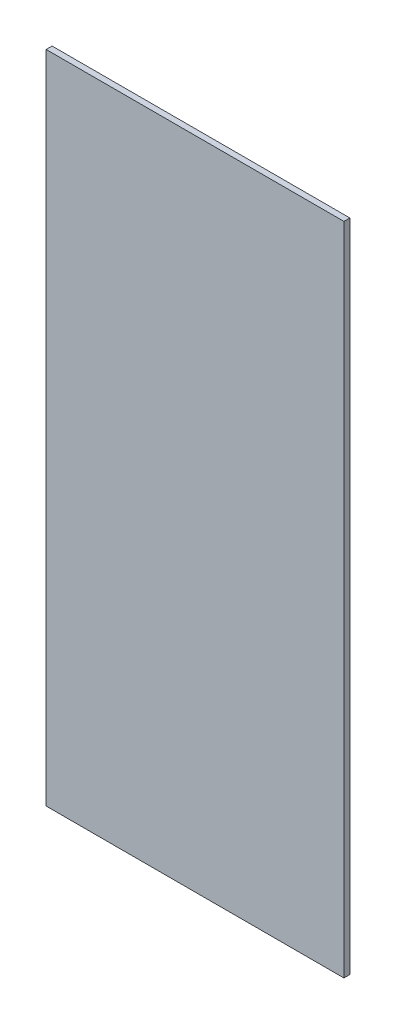
SolidWorks part; units mm, degrees
ref_plane "Спереди" through (0, 0, 0) normal (0, 0, 1) x (1, 0, 0)
ref_plane "Сверху" through (0, 0, 0) normal (0, 1, 0) x (1, 0, 0)
ref_plane "Справа" through (0, 0, 0) normal (1, 0, 0) x (0, 0, -1)
sketch "Эскиз1" plane through (0, 0, 0) normal (0, 0, 1) x (1, 0, 0)
  line L1 (0, 0) -> (500, 0)
  line L2 (0, 0) -> (0, 1100)
  line L3 (0, 1100) -> (500, 1100)
  line L4 (500, 0) -> (500, 1100)
  dimension "D1" = 500
  dimension "D2" = 1100
extrude "Бобышка-Вытянуть1" add sketch "Эскиз1" along normal blind 10 contours L2 L1 L4 L3
